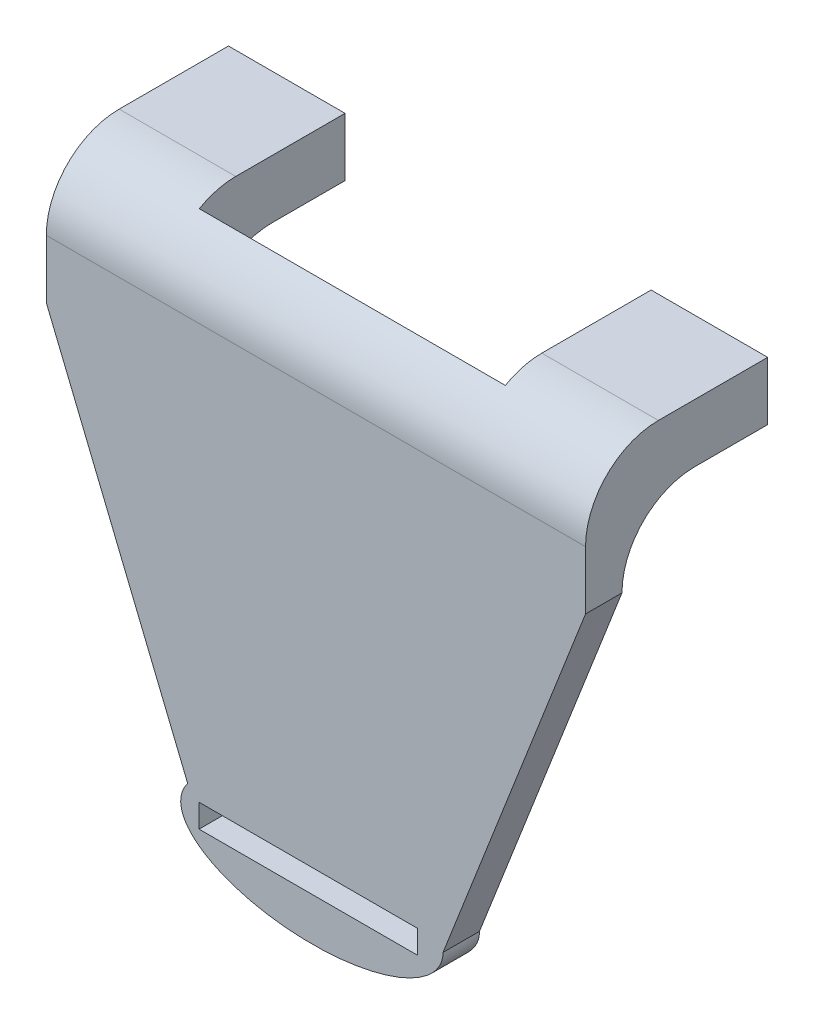
SolidWorks part; units mm, degrees
ref_plane "Front Plane" through (0, 0, 0) normal (0, 0, 1) x (1, 0, 0)
ref_plane "Top Plane" through (0, 0, 0) normal (0, 1, 0) x (1, 0, 0)
ref_plane "Right Plane" through (0, 0, 0) normal (1, 0, 0) x (0, 0, -1)
sketch "Plate Feature Sketch" plane through (0, 0, 0) normal (0, 0, 1) x (1, 0, 0)
  line L0 (-36, 18) -> (-36, 0)
  line L4 (38, 0) -> (38, 18)
  line L5 (38, 18) -> (-36, 18)
  line L6 (-36, 0) -> (-15.5537, -50)
  line L7 (-15.5537, -50) -> (18.4463, -50)
  line L8 (18.4463, -50) -> (38, 0)
  dimension "D1" = 68
  dimension "D2" = 34
  dimension "D3" = 74
extrude "Plate Feature" add sketch "Plate Feature Sketch" along normal blind 5 contours L8 L4 L5 L0 L6 L7
sketch "Strap Feature Sketch" plane through (0, 0, 0) normal (0, 0, 1) x (1, 0, 0)
  ellipse E0 centre (0.4463, -50) end of major axis (18.4463, -50) minor radius 8
extrude "Strap Feature" add sketch "Strap Feature Sketch" along normal blind 5 contours E0
sketch "Strap Cut Sketch" plane through (0, 0, 0) normal (0, 0, 1) x (1, 0, 0)
  line L1 (-15.0349, -48.8917) -> (14.9651, -48.8917)
  line L2 (-15.0349, -48.8917) -> (-15.0349, -52.0899)
  line L3 (-15.0349, -52.0899) -> (14.9651, -52.0899)
  line L4 (14.9651, -48.8917) -> (14.9651, -52.0899)
  line L5 (-15.0349, -48.8917) -> (14.9651, -52.0899) construction
  line L6 (-15.0349, -52.0899) -> (14.9651, -48.8917) construction
  point P0 (-0.0349, -50.4908)
  dimension "D1" = 30
  dimension "D2" = 3.1982
extrude "Strap Cut" cut sketch "Strap Cut Sketch" along normal blind 5
sketch "Left Leg Feature Sketch" plane through (0, 0, 0) normal (0, 0, 1) x (1, 0, 0)
  line L0 (38, 10) -> (22, 10)
  line L1 (38, 10) -> (38, 18)
  line L2 (22, 10) -> (22, 18)
  line L3 (38, 18) -> (22, 18)
  line L4 (38, 0) -> (38, 18) construction
  line L5 (38, 18) -> (-36, 18) construction
  dimension "D1" = 0
  dimension "D2" = 8
  dimension "D3" = 0
extrude "Left Leg Feature" add sketch "Left Leg Feature Sketch" against normal blind 20 contours L2 L3 L1 L0
sketch "Right Leg Feature Sketch" plane through (0, 0, 0) normal (0, 0, 1) x (1, 0, 0)
  line L0 (-36, 10) -> (-20, 10)
  line L1 (-36, 10) -> (-36, 18)
  line L2 (-20, 10) -> (-20, 18)
  line L3 (-36, 18) -> (-20, 18)
  line L5 (38, 18) -> (-36, 18) construction
  dimension "D1" = 0
  dimension "D2" = 8
extrude "Right Leg Feature" add sketch "Right Leg Feature Sketch" against normal blind 20 contours L0 L2 L3 L1
sketch "Tab Cut Sketch" plane through (0, 10, 0) normal (0, 1, 0) x (1, 0, 0)
  line L0 (-36, -5) -> (-36, 20) construction
  line L1 (-32, 20) -> (-24, 20)
  line L2 (-32, 20) -> (-32, 5)
  line L3 (-32, 5) -> (-24, 5)
  line L4 (-24, 20) -> (-24, 5)
  line L5 (-32, 20) -> (-24, 5) construction
  line L6 (-32, 5) -> (-24, 20) construction
  line L7 (22, 20) -> (22, 0) construction
  line L8 (26, 20) -> (34, 20)
  line L9 (26, 20) -> (26, 5)
  line L10 (26, 5) -> (34, 5)
  line L11 (34, 20) -> (34, 5)
  line L12 (26, 20) -> (34, 5) construction
  line L13 (26, 5) -> (34, 20) construction
  point P0 (-28, 12.5)
  point P5 (30, 12.5)
  dimension "D1" = 8
  dimension "D2" = 15
  dimension "D3" = 4
  dimension "D4" = 8
  dimension "D5" = 4
extrude "Tab Cut" cut sketch "Tab Cut Sketch" along normal blind 5
fillet "Fillet1" radius 10 1 edges at (1, 18, 5)
fillet "Fillet2" radius 10 1 edges at (-28, 10, 0)
fillet "Fillet3" radius 10 1 edges at (30, 10, 0)
